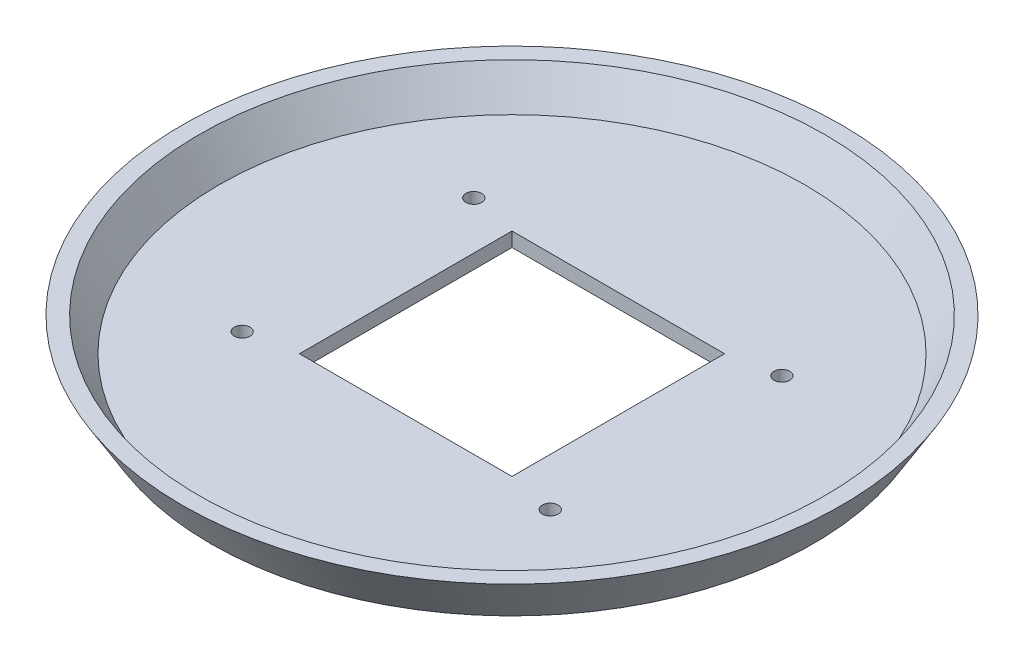
SolidWorks part; units mm, degrees
ref_plane "Front Plane" through (0, 0, 0) normal (0, 0, 1) x (1, 0, 0)
ref_plane "Top Plane" through (0, 0, 0) normal (0, 1, 0) x (1, 0, 0)
ref_plane "Right Plane" through (0, 0, 0) normal (1, 0, 0) x (0, 0, -1)
sketch "Sketch1" plane through (0, 0, 0) normal (0, 0, 1) x (1, 0, 0)
  line L0 (0, 0) -> (63, 0)
  line L1 (63, 0) -> (69, 10)
  line L6 (0, 3) -> (61.3014, 3)
  line L7 (61.3014, 3) -> (65.5014, 10)
  line L8 (69, 10) -> (65.5014, 10)
  line L9 (0, 0) -> (0, 3)
  line L10 (61.3014, 3) -> (66.4275, 11.5435) construction
  dimension "D1" = 69
  dimension "D2" = 63
  dimension "D3" = 10
  dimension "D4" = 3
revolve "Revolve1" add sketch "Sketch1" angle 360 about L9
sketch "Sketch2" plane through (0, 3, 0) normal (0, 1, 0) x (1, 0, 0)
  line L1 (-22.25, 22.25) -> (22.25, 22.25)
  line L2 (-22.25, 22.25) -> (-22.25, -22.25)
  line L3 (-22.25, -22.25) -> (22.25, -22.25)
  line L4 (22.25, 22.25) -> (22.25, -22.25)
  line L5 (-22.25, 22.25) -> (22.25, -22.25) construction
  line L6 (-22.25, -22.25) -> (22.25, 22.25) construction
  circle A0 centre (-32.25, 24.25) radius 1.65
  circle A1 centre (32.25, 24.25) radius 1.65
  circle A2 centre (-32.25, -24.25) radius 1.65
  circle A3 centre (32.25, -24.25) radius 1.65
  point P0 (0, 0)
  dimension "D3" = 3.3
  dimension "D5" = 10
  dimension "D6" = 10
  dimension "D7" = 10
  dimension "D9" = 2
  dimension "D10" = 2
  dimension "D11" = 2
  dimension "D1" = 44.5
  dimension "D2" = 44.5
  dimension "D4" = 10
  dimension "D8" = 2
  dimension "D12" = 0
  dimension "D13" = 0
extrude "Cut-Extrude1" cut sketch "Sketch2" against normal through all
